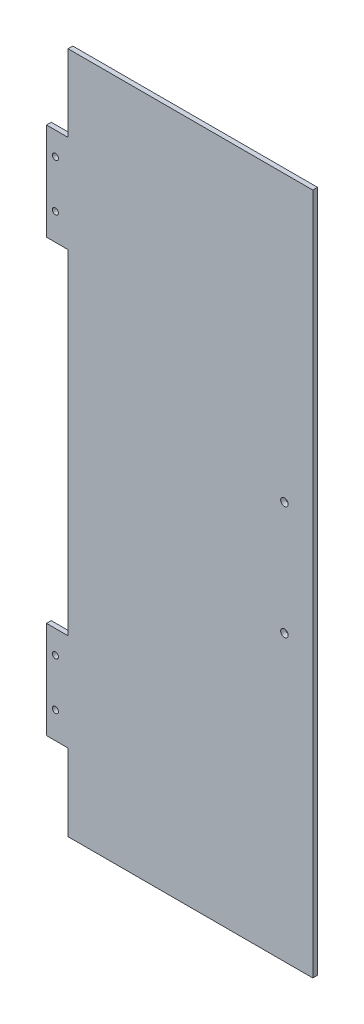
SolidWorks part; units mm, degrees
ref_plane "Front Plane" through (0, 0, 0) normal (0, 0, 1) x (1, 0, 0)
ref_plane "Top Plane" through (0, 0, 0) normal (0, 1, 0) x (1, 0, 0)
ref_plane "Right Plane" through (0, 0, 0) normal (1, 0, 0) x (0, 0, -1)
sketch "Sketch1" plane through (0, 0, 0) normal (0, 0, 1) x (1, 0, 0)
  line L0 (-164.338, 229.108) -> (0, 229.108) construction
  line L1 (0, 0) -> (-164.338, 0)
  line L2 (0, 0) -> (0, 458.216)
  line L3 (0, 458.216) -> (-164.338, 458.216)
  line L4 (-164.338, 0) -> (-164.338, 458.216)
  line L5 (-82.169, 458.216) -> (-82.169, 0) construction
  line L6 (-164.338, 116.84) -> (-178.816, 116.84)
  line L7 (-164.338, 51.562) -> (-178.816, 51.562)
  line L8 (-178.816, 116.84) -> (-178.816, 51.562)
  line L9 (-303.3951, 65.151) -> (-302.9884, 65.151)
  line L10 (-164.338, 406.654) -> (-178.816, 406.654)
  line L11 (-164.338, 341.376) -> (-178.816, 341.376)
  line L12 (-178.816, 341.376) -> (-178.816, 406.654)
  line L13 (-164.338, 341.376) -> (-164.338, 406.654)
  dimension "D1" = 458.216
  dimension "D2" = 164.338
  dimension "D3" = 51.562
  dimension "D4" = 65.278
  dimension "D5" = 14.478
extrude "Boss-Extrude3" add sketch "Sketch1" along normal blind 3.175 contours L4 L1 L2 L3 | L6 L8 L7 L4 | L13 L10 L12 L11 region at (-82.169, 229.108, 0) region at (-171.577, 84.201, 0)
sketch "Sketch2" plane through (0, 0, 3.175) normal (0, 0, 1) x (1, 0, 0)
  line L0 (-164.338, 229.108) -> (0, 229.108) construction
  line L1 (-164.338, 116.84) -> (-164.338, 341.376) construction
  line L2 (0, 0) -> (0, 458.216) construction
  line L3 (-178.816, 116.84) -> (-178.816, 51.562) construction
  line L4 (-164.338, 51.562) -> (-178.816, 51.562) construction
  line L5 (-164.338, 116.84) -> (-178.816, 116.84) construction
  line L6 (-164.338, 341.376) -> (-178.816, 341.376) construction
  line L7 (-164.338, 406.654) -> (-178.816, 406.654) construction
  line L8 (-178.816, 341.376) -> (-178.816, 406.654) construction
  circle A0 centre (-172.8149, 69.4938) radius 2.032
  circle A1 centre (-172.8149, 101.2438) radius 2.032
  circle A2 centre (-172.8149, 391.16) radius 2.032
  circle A3 centre (-172.8149, 359.41) radius 2.032
  dimension "D1" = 4.064
  dimension "D2" = 4.064
  dimension "D3" = 31.75
  dimension "D4" = 6.0011
  dimension "D5" = 17.9318
  dimension "D6" = 15.5962
  dimension "D8" = 15.494
  dimension "D9" = 31.75
  dimension "D10" = 6.0011
  dimension "D11" = 4.064
  dimension "D12" = 4.064
  dimension "D7" = 18.034
extrude "Cut-Extrude1" cut sketch "Sketch2" against normal through all
sketch "Sketch4" plane through (0, 0, 3.175) normal (0, 0, 1) x (1, 0, 0)
  line L0 (-210.832, 229.0858) -> (93.968, 229.0858) construction
  line L1 (-210.832, 495.7858) -> (-210.832, -37.6142) construction
  line L2 (93.968, -37.6142) -> (93.968, 495.7858) construction
  line L3 (-19.05, 190.9858) -> (-19.05, 267.1858) construction
  line L4 (0, 0) -> (0, 458.216) construction
  circle A0 centre (-19.05, 190.9858) radius 2.54
  circle A1 centre (-19.05, 267.1858) radius 2.54
  point P8 (-19.05, 229.0858)
  dimension "D2" = 19.05
  dimension "D3" = 5.08
  dimension "D4" = 5.08
  dimension "D1" = 76.2
extrude "Cut-Extrude3" cut sketch "Sketch4" against normal through all
